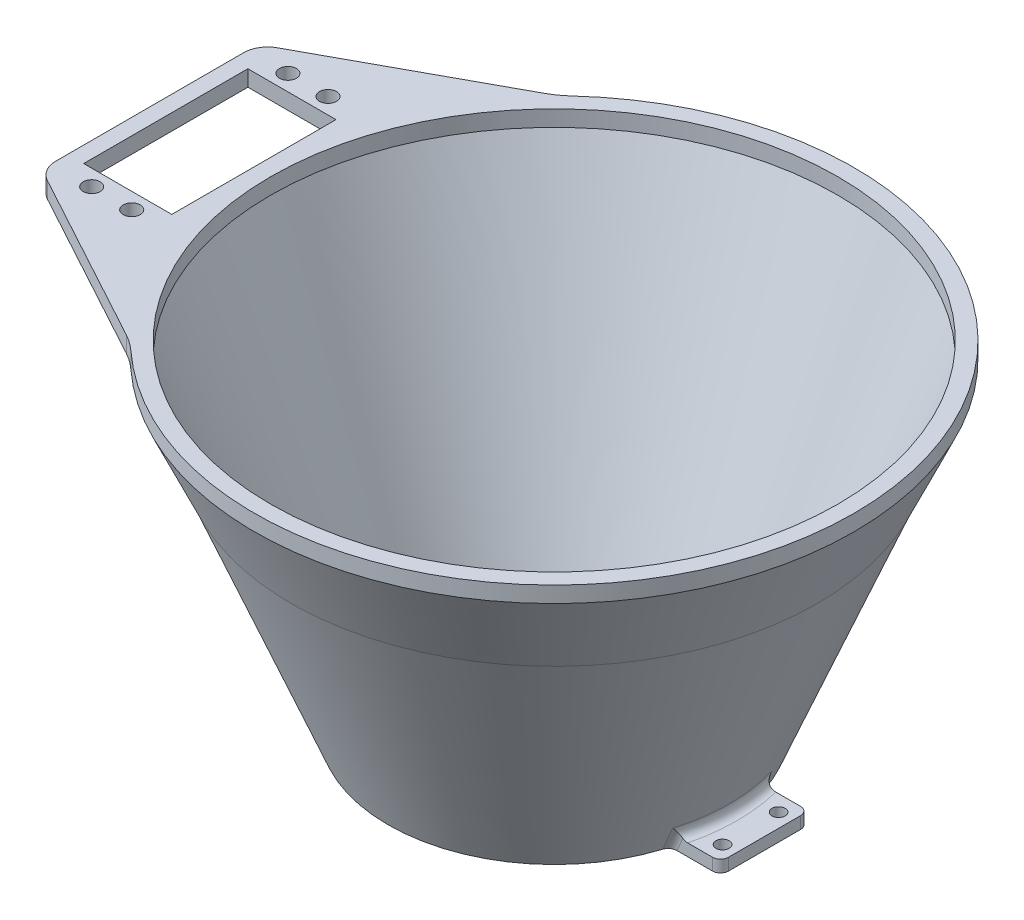
SolidWorks part; units mm, degrees
ref_plane "Front Plane" through (0, 0, 0) normal (0, 0, 1) x (1, 0, 0)
ref_plane "Top Plane" through (0, 0, 0) normal (0, 1, 0) x (1, 0, 0)
ref_plane "Right Plane" through (0, 0, 0) normal (1, 0, 0) x (0, 0, -1)
sketch "Sketch2" plane through (0, 0, 0) normal (0, 0, 1) x (1, 0, 0)
  line L0 (0, 0) -> (38.5, 0) construction
  line L1 (38.5, 0) -> (70.8221, 80)
  line L2 (38.5, 0) -> (41.5, 0) construction
  line L3 (41.5, 0) -> (73.8221, 80)
  line L4 (70.8221, 80) -> (73.8221, 80)
  line L5 (0, 0) -> (0, 42.1787) construction
  line L6 (38.5, 0) -> (41.5, 0)
  point P6 (76.0242, 80)
  dimension "D1" = 38.5
  dimension "D2" = 41.5
  dimension "D3" = 80
  dimension "D4" = 112
  dimension "D5" = 80
revolve "Revolve1" add sketch "Sketch2" angle 360 about L5
sketch "Sketch3" plane through (0, 0, 0) normal (0, -1, 0) x (1, 0, 0)
  line L0 (-52.5156, 11) -> (-40.0156, 11)
  line L1 (-52.5156, 11) -> (-52.5156, -11)
  line L2 (-52.5156, -11) -> (-40.0156, -11)
  line L3 (-52.5156, 0) -> (0, 0) construction
  line L4 (0, 0) -> (0, 25.3337) construction
  line L5 (52.5156, -11) -> (40.0156, -11)
  line L6 (52.5156, 11) -> (52.5156, -11)
  line L7 (52.5156, 11) -> (40.0156, 11)
  circle A0 centre (0, 0) radius 41.5 construction
  circle A1 centre (0, 0) radius 41.5 construction
  circle A2 centre (-49.0156, -7) radius 1.65
  arc A3 (-40.0156, -11) -> (-40.0156, 11) centre (0, 0) cw
  circle A4 centre (-49.0156, 7) radius 1.65
  circle A5 centre (49.0156, 7) radius 1.65
  arc A6 (40.0156, -11) -> (40.0156, 11) centre (0, 0) ccw
  circle A7 centre (49.0156, -7) radius 1.65
  dimension "D2" = 3.3
  dimension "D1" = 22
  dimension "D3" = 7
  dimension "D4" = 3.5
  dimension "D5" = 12.5
extrude "Boss-Extrude1" add sketch "Sketch3" against normal blind 3
fillet "Fillet1" radius 2 10 edges at (52.5156, 1.5, -11) (52.5156, 1.5, 11) (-52.5156, 1.5, 11) (-52.5156, 1.5, -11) (42.7121, 3, 0) (-42.7121, 3, 0)
sketch "Sketch4" plane through (0, 80, 0) normal (0, 1, 0) x (1, 0, 0)
  line L0 (-86, 34.5374) -> (-86, -37.4895) construction
  line L1 (-108.9765, 0) -> (0, 0) construction
  line L2 (-101, 27) -> (-20, 71.0613)
  line L3 (-97, -20.5) -> (-75, -20.5)
  line L4 (-97, -20.5) -> (-97, 20.5)
  line L5 (-97, 20.5) -> (-75, 20.5)
  line L6 (-75, -20.5) -> (-75, 20.5)
  line L7 (-97, -20.5) -> (-75, 20.5) construction
  line L8 (-97, 20.5) -> (-75, -20.5) construction
  line L9 (-101, -27) -> (-71, -27) construction
  line L10 (-101, -27) -> (-101, 27)
  line L11 (-101, 27) -> (-71, 27) construction
  line L12 (-71, -27) -> (-71, 27) construction
  line L13 (-101, -27) -> (-71, 27) construction
  line L14 (-101, 27) -> (-71, -27) construction
  line L15 (-101, -27) -> (-20, -71.0613)
  line L17 (-20, -71.0613) -> (-20, -59.4685)
  circle A0 centre (-91, 24.5) radius 2.125
  circle A1 centre (-81, 24.5) radius 2.125
  circle A2 centre (-81, -24.5) radius 2.125
  circle A3 centre (-91, -24.5) radius 2.125
  circle A4 centre (0, 0) radius 73.8221 construction
  circle A8 centre (0, 0) radius 70.8221 construction
  circle A9 centre (0, 0) radius 70.8221
  arc A10 (-48.7907, -55.4001) -> (-48.7907, 55.4001) centre (0, 0) ccw
  point P13 (-86, 0)
  point P16 (-86, 0)
  circle M13 centre (0, 0) radius 70.8221
  circle M14 centre (0, 0) radius 73.8221
  dimension "D1" = 4.25
  dimension "D2" = 5
  dimension "D3" = 24.5
  dimension "D4" = 86
  dimension "D5" = 22
  dimension "D6" = 41
  dimension "D7" = 54
  dimension "D8" = 30
  dimension "D9" = 20
extrude "Boss-Extrude2" add sketch "Sketch4" along normal blind 4 separate body contours L15 L2 M14 M13 | L10 L15 L2 A1 A0 L6 L3 L4 L5 A2 A3 M14 region at (-74.3101, 80, -40.1241) region at (-34.2956, 80, -63.0473)
sketch "Sketch6" plane through (0, 0, 0) normal (0, 0, 1) x (1, 0, 0)
  line L0 (-73.8221, 80) -> (-74.8221, 80)
  line L1 (-101, 80) -> (-20, 80) construction
  line L2 (-74.8221, 80) -> (-65.7416, 60)
  line L3 (-73.8221, 80) -> (-43.8228, 5.7492) construction
  line L4 (-65.7416, 60) -> (-73.8221, 80)
  line L5 (0, 0) -> (0, 90.5033) construction
  dimension "D1" = 1
  dimension "D2" = 20
revolve "Revolve5" add sketch "Sketch6" angle 360 about L5
sketch "Sketch7" plane through (0, 80, 0) normal (0, 1, 0) x (1, 0, 0)
  line L2 (-52.3377, 53.4706) -> (-20, 71.0613)
  line L3 (-20, -71.0613) -> (-52.3377, -53.4706)
  line L4 (-52.3377, 53.4706) -> (-20, 71.0613)
  line L5 (-20, -71.0613) -> (-52.3377, -53.4706)
  arc A2 (-52.3377, -53.4706) -> (-52.3377, 53.4706) centre (0, 0) ccw
  arc A3 (-20, -71.0613) -> (-20, 71.0613) centre (0, 0) ccw
  arc A4 (-52.3377, -53.4706) -> (-52.3377, 53.4706) centre (0, 0) ccw
  arc A5 (-20, -71.0613) -> (-20, 71.0613) centre (0, 0) ccw
  dimension "D1" = 0
extrude "Boss-Extrude3" add sketch "Sketch7" along normal blind 4
fillet "Fillet4" radius 20 2 edges at (-52.3377, 82, 53.4706) (-52.3377, 82, -53.4706)
fillet "Fillet5" radius 6 2 edges at (-101, 82, -27) (-101, 82, 27)
